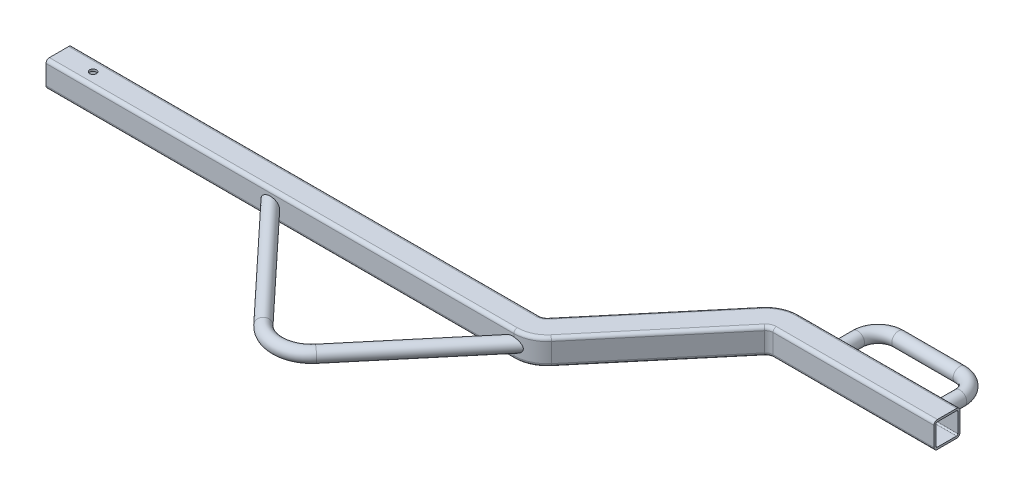
SolidWorks part; units mm, degrees
material "5052-H38, Rod (SS)"
ref_plane "Front Plane" through (0, 0, 0) normal (0, 0, 1) x (1, 0, 0)
ref_plane "Top Plane" through (0, 0, 0) normal (0, 1, 0) x (1, 0, 0)
ref_plane "Right Plane" through (0, 0, 0) normal (1, 0, 0) x (0, 0, -1)
sketch "Sketch2" plane through (0, 0, 0) normal (1, 0, 0) x (0, 0, -1)
  line L1 (-14.05, -19.05) -> (14.05, -19.05)
  line L2 (-19.05, -14.05) -> (-19.05, 14.05)
  line L3 (-14.05, 19.05) -> (14.05, 19.05)
  line L4 (19.05, -14.05) -> (19.05, 14.05)
  line L5 (-19.05, -19.05) -> (19.05, 19.05) construction
  line L6 (-19.05, 19.05) -> (19.05, -19.05) construction
  arc A0 (19.05, -14.05) -> (14.05, -19.05) centre (14.05, -14.05) cw
  arc A1 (-14.05, -19.05) -> (-19.05, -14.05) centre (-14.05, -14.05) cw
  arc A2 (-19.05, 14.05) -> (-14.05, 19.05) centre (-14.05, 14.05) cw
  arc A3 (14.05, 19.05) -> (19.05, 14.05) centre (14.05, 14.05) cw
  point P0 (0, 0)
  dimension "D3" = 5
  dimension "D1" = 38.1
  dimension "D2" = 38.1
sketch3d "3DSketch2"
  line L0 (708.9921, 0, -10.7164) -> (851.7048, 0, -180.7947)
  line L1 (874.6861, 0, -191.5111) -> (1110.6969, 0, -191.5111)
  line L3 (0, 0, 0) -> (686.0108, 0, 0)
  line L4 (700, 0, 0) -> (828.2254, 0, 0) construction
  arc A0 (851.7048, 0, -180.7947) -> (874.6861, 0, -191.5111) centre (874.6861, 0, -161.5111) ccw
  arc A1 (686.0108, 0, 0) -> (708.9921, 0, -10.7164) centre (686.0108, 0, -30) ccw
  point P9 (860.6969, 0, -191.5111)
  point P10 (874.6861, -30, -161.5111)
  point P13 (700, 0, 0)
  point P15 (686.0108, 30, -30)
  dimension "D5" = 30
  dimension "D6" = 30
  dimension "D1" = 700
  dimension "D2" = 250
  dimension "D3" = 130
  dimension "D4" = 250
sweep "Sweep-Thin3" add profiles "Sketch2" path "3DSketch2" parameters "D1"=3
sketch "Sketch21" plane through (0, 0, 0) normal (0, 1, 0) x (1, 0, 0)
  line L0 (0, 0) -> (686.0108, 0) construction
  circle A0 centre (50, 0) radius 5
  dimension "D1" = 10
  dimension "D2" = 50
extrude "Cut-Extrude3" cut sketch "Sketch21" against normal through all both and the other way through all
sketch "Sketch22" [suppressed] plane through (0, 0, 0) normal (0, 0, 1) x (1, 0, 0)
ref_plane "Plane1" [suppressed] through (0, -210, 0) normal (0, 1, 0) x (1, 0, 0)
ref_plane "Plane2" through (0, 0, 0) normal (0, -1, 0) x (1, 0, 0)
sketch "Sketch24" plane through (0, 0, -210.5611) normal (0, 0, -1) x (-1, 0, 0)
  line L0 (-874.6861, 0) -> (-1110.6969, 0) construction
  line L1 (-874.6861, -14.05) -> (-874.6861, 14.05) construction
  line L2 (-1110.6969, -14.05) -> (-1110.6969, 14.05) construction
sketch "Sketch25" plane through (0, 0, 0) normal (0, -1, 0) x (1, 0, 0)
  line L0 (874.6861, -210.5611) -> (1110.6969, -210.5611) construction
  line L1 (1080.6969, -210.5611) -> (1080.6969, -240.5611)
  line L2 (1050.6969, -270.5611) -> (960.6969, -270.5611)
  line L3 (930.6969, -240.5611) -> (930.6969, -210.5611)
  arc A0 (1080.6969, -240.5611) -> (1050.6969, -270.5611) centre (1050.6969, -240.5611) cw
  arc A1 (960.6969, -270.5611) -> (930.6969, -240.5611) centre (960.6969, -240.5611) cw
  point P10 (1080.6969, -270.5611)
  point P13 (930.6969, -270.5611)
  dimension "D3" = 30
  dimension "D1" = 150
  dimension "D2" = 60
  dimension "D4" = 30
sweep "Sweep-Thin4" add path "Sketch25" circular profile diameter 20 parameters "D1"=3, "D3"=20
sketch "Sketch26" plane through (0, 0, 0) normal (0, 1, 0) x (1, 0, 0)
  line L0 (708.9921, 10.7164) -> (552.4276, -175.87)
  line L1 (477.6092, -177.8857) -> (311.2253, 0)
  line L3 (708.9921, 10.7164) -> (851.7048, 180.7947) construction
  line L4 (0, 0) -> (686.0108, 0) construction
  arc A0 (477.6092, -177.8857) -> (552.4276, -175.87) centre (514.1253, -143.7306) ccw
  point P10 (516.1558, -219.097)
  dimension "D3" = 50
  dimension "D1" = 300
  dimension "D2" = 300
sweep "Sweep-Thin5" add path "Sketch26" circular profile diameter 20 parameters "D1"=1, "D3"=20
